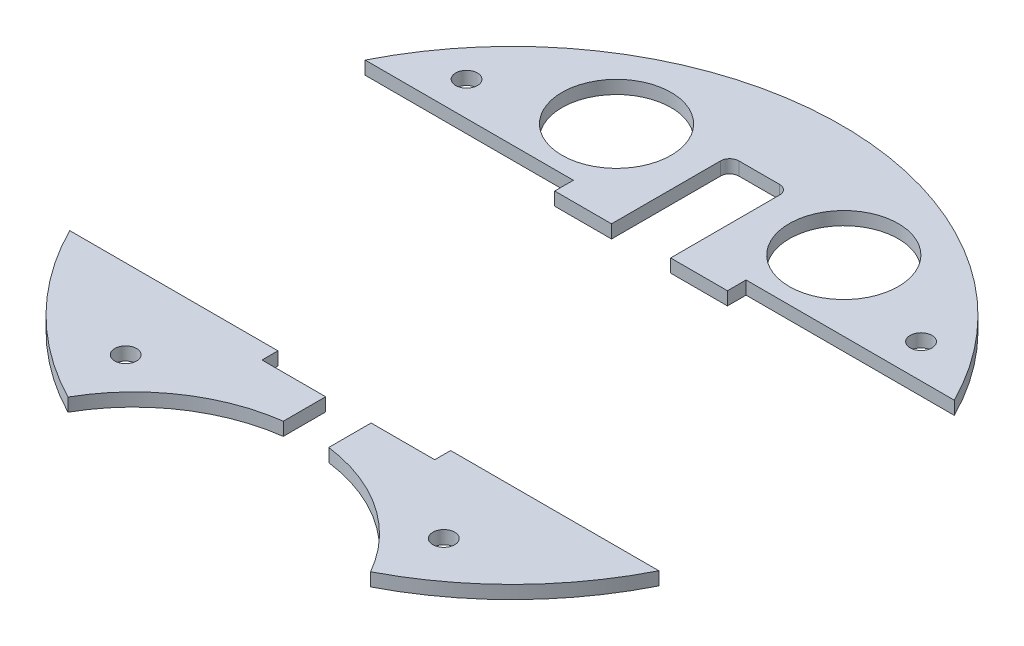
SolidWorks part; units mm, degrees
material "Acrylic (Medium-high impact)"
ref_plane "Front Plane" through (0, 0, 0) normal (0, 0, 1) x (1, 0, 0)
ref_plane "Top Plane" through (0, 0, 0) normal (0, 1, 0) x (1, 0, 0)
ref_plane "Right Plane" through (0, 0, 0) normal (1, 0, 0) x (0, 0, -1)
sketch "Sketch1" plane through (0, 0, 0) normal (0, 1, 0) x (1, 0, 0)
  line L0 (0, -83.2398) -> (-33.2911, -64.4046) construction
  line L1 (0, -83.2398) -> (0, 0) construction
  arc A0 (33.2911, -64.4046) -> (-33.2911, -64.4046) centre (0, 0) ccw
  arc A1 (33.2911, -64.4046) -> (-33.2911, -64.4046) centre (0, -83.2398) ccw
  dimension "D1" = 145
  dimension "D2" = 76.5
  dimension "D3" = 60.5
extrude "Boss-Extrude1" add sketch "Sketch1" along normal blind 2.9
sketch "solenoid placement" plane through (0, 2.9, 0) normal (0, 1, 0) x (1, 0, 0)
  line L4 (-19, -36) -> (19, -36)
  line L5 (-19, 28.4) -> (-19, -36)
  line L6 (19, 28.4) -> (-19, 28.4)
  line L7 (19, -36) -> (19, 28.4)
  line L8 (-19, -36) -> (19, -36)
  line L9 (-19, 28.4) -> (-19, -36)
  line L10 (19, 28.4) -> (-19, 28.4)
  line L11 (19, -36) -> (19, 28.4)
  dimension "D1" = 0
extrude "Cut-Extrude1" cut sketch "solenoid placement" against normal through all
sketch "Sketch4" plane through (0, 2.9, 0) normal (0, 1, 0) x (1, 0, 0)
  line L6 (-6.5, 28.1) -> (6.5, 28.1)
  line L7 (6.5, 28.1) -> (6.5, 52.4)
  line L8 (4.5, 54.4) -> (-4.5, 54.4)
  line L9 (-6.5, 52.4) -> (-6.5, 28.1)
  line L10 (-6.5, 28.1) -> (6.5, 28.1)
  line L11 (6.5, 28.1) -> (6.5, 52.4)
  line L12 (4.5, 54.4) -> (-4.5, 54.4)
  line L13 (-6.5, 52.4) -> (-6.5, 28.1)
  arc A4 (6.5, 52.4) -> (4.5, 54.4) centre (4.5, 52.4) ccw
  arc A5 (6.5, 52.4) -> (4.5, 54.4) centre (4.5, 52.4) ccw
  arc A6 (-4.5, 54.4) -> (-6.5, 52.4) centre (-4.5, 52.4) ccw
  arc A7 (-4.5, 54.4) -> (-6.5, 52.4) centre (-4.5, 52.4) ccw
  dimension "D1" = 0
extrude "Cut-Extrude4" cut sketch "Sketch4" against normal through all
sketch "Sketch5" plane through (0, 2.9, 0) normal (0, 1, 0) x (1, 0, 0)
  circle A1 centre (25, 48) radius 12
  circle A2 centre (25, 48) radius 12
  circle A3 centre (-25, 48) radius 12
  circle A4 centre (-25, 48) radius 12
  dimension "D1" = 0
  dimension "D2" = 0
extrude "Cut-Extrude5" cut sketch "Sketch5" against normal through all
sketch "Sketch6" plane through (0, 2.9, 0) normal (0, 1, 0) x (1, 0, 0)
  circle A1 centre (35, -50) radius 2.4
  circle A2 centre (35, -50) radius 2.4
  circle A3 centre (-35, -50) radius 2.4
  circle A4 centre (-35, -50) radius 2.4
  circle A5 centre (-50, 40) radius 2.4
  circle A6 centre (-50, 40) radius 2.4
  circle A7 centre (50, 40) radius 2.4
  circle A8 centre (50, 40) radius 2.4
  dimension "D1" = 0
  dimension "D2" = 0
  dimension "D3" = 0
  dimension "D4" = 0
extrude "Cut-Extrude6" cut sketch "Sketch6" against normal through all
sketch "Sketch7" plane through (0, 2.9, 0) normal (0, 1, 0) x (1, 0, 0)
  line L1 (-5, 0) -> (5, 0)
  line L2 (-5, 0) -> (-5, -62.8025)
  line L3 (-5, -62.8025) -> (5, -62.8025)
  line L4 (5, 0) -> (5, -62.8025)
  dimension "D1" = 10
extrude "Cut-Extrude7" cut sketch "Sketch7" against normal through all
sketch "Sketch3" plane through (0, 2.9, 0) normal (0, 1, 0) x (1, 0, 0)
  line L0 (-19, 28.4) -> (19, 28.4)
  line L1 (-72.5, -32.5) -> (72.5, -32.5)
  line L2 (-72.5, -32.5) -> (-72.5, 32.5)
  line L3 (-72.5, 32.5) -> (-19, 32.5)
  line L4 (72.5, -32.5) -> (72.5, 32.5)
  line L5 (-72.5, -32.5) -> (72.5, 32.5) construction
  line L6 (-72.5, 32.5) -> (72.5, -32.5) construction
  line L7 (19, 28.4) -> (19, 32.5)
  line L8 (-19, 28.4) -> (-19, 32.5)
  line L9 (19, 32.5) -> (72.5, 32.5)
  arc A0 (33.2911, -64.4046) -> (-33.2911, -64.4046) centre (0, 0) ccw construction
  point P0 (0, 0)
  dimension "D1" = 65
extrude "Cut-Extrude3" cut sketch "Sketch3" against normal through all
equation "\"smallPulleyTeeth\"= 15"
equation "\"largePulleyTeeth\"= 30"
equation "\"eighthThick\"= 2.9mm"
equation "\"sixteenthThick\" = 1.7mm"
equation "\"quarterThick\"=6.0mm"
equation "\"OD\" = 145mm"
equation "\"puckAngle\" = 60.5deg"
equation "\"D1@Sketch1\"=\"OD\""
equation "\"puckDiam\" = 76.5mm"
equation "\"D2@Sketch1\"=\"puckDiam\""
equation "\"D3@Sketch1\"=\"puckAngle\""
equation "\"D1@Boss-Extrude1\"=\"eighthThick\""
equation "\"axlePress\" = 5.9mm"
equation "\"press\" = 0.2mm"
equation "\"wheelClear\" = 0.3mm"
equation "\"10-32clear\" = 4.8mm"
equation "\"6-32clear\" = 3.3mm"
equation "\"8-32clear\" = 4.0mm"
equation "\"wheelHeight\" = 22mm"
equation "\"wheelWell\" = 65mm"
equation "\"D1@Sketch3\"=\"wheelWell\""
